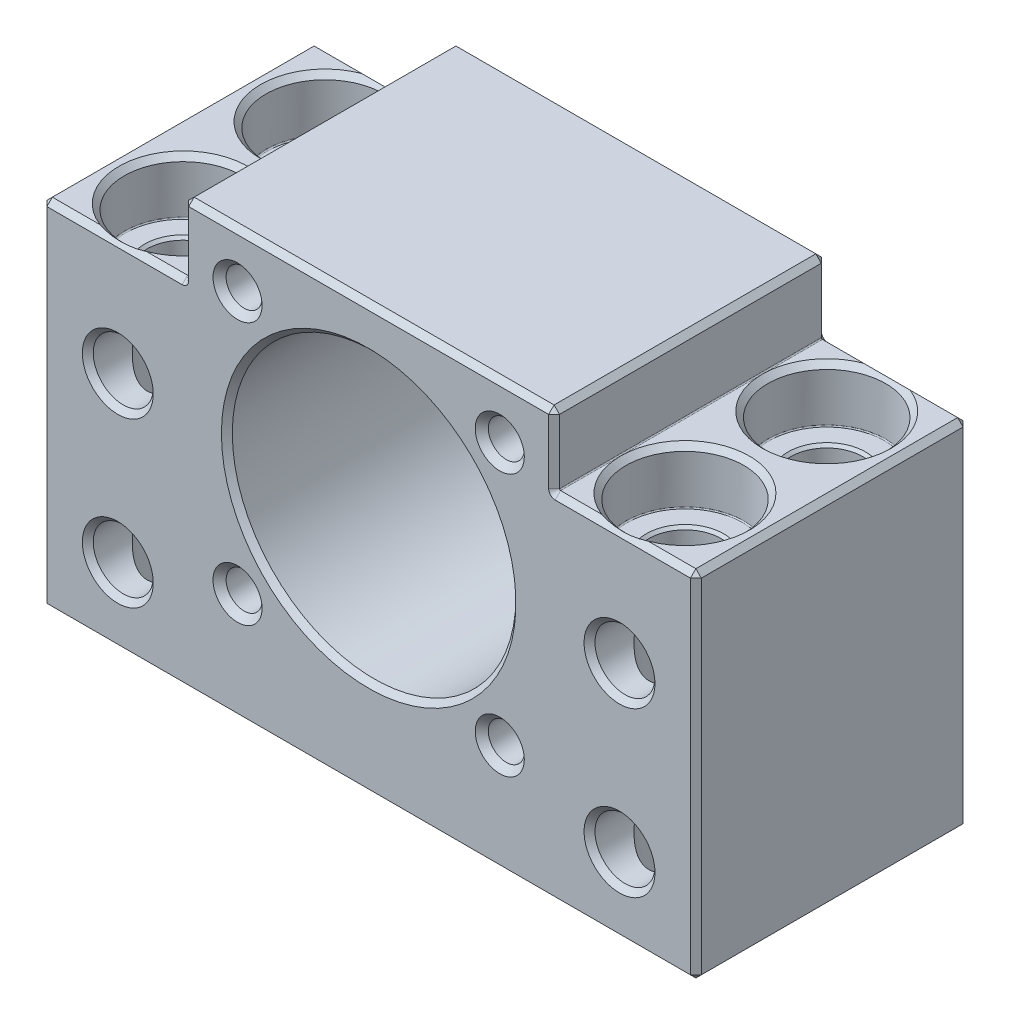
SolidWorks part; units mm, degrees
material "1023 Carbon Steel Sheet (SS)"
ref_plane "Front Plane" through (0, 0, 0) normal (0, 0, 1) x (1, 0, 0)
ref_plane "Top Plane" through (0, 0, 0) normal (0, 1, 0) x (1, 0, 0)
ref_plane "Right Plane" through (0, 0, 0) normal (1, 0, 0) x (0, 0, -1)
sketch "BK Body Sketch" plane through (0, 0, 0) normal (0, 0, 1) x (1, 0, 0)
  line L0 (30, -22) -> (-30, -22)
  line L1 (-30, -22) -> (-30, 10.5)
  line L2 (-30, 10.5) -> (-17, 10.5)
  line L3 (-17, 10.5) -> (-17, 17)
  line L4 (-17, 17) -> (17, 17)
  line L5 (17, 17) -> (17, 10.5)
  line L6 (17, 10.5) -> (30, 10.5)
  line L7 (30, 10.5) -> (30, -22)
  point P2 (0, -22)
  point P9 (0, 17)
  dimension "B" = 60
  dimension "B1" = 34
  dimension "H2" = 22
  dimension "H1" = 32.5
  dimension "H" = 39
extrude "BK Body" add sketch "BK Body Sketch" along normal mid plane 25
sketch "BK B-Flange" plane through (0, 0, 0) normal (0, 0, 1) x (1, 0, 0)
  circle A0 centre (0, 0) radius 11
  dimension "DOS" = 22
extrude "BK Flange" cut sketch "BK B-Flange" against normal through all both and the other way through all
sketch "BK B-Hole" plane through (0, 0, 12.5) normal (0, 0, 1) x (1, 0, 0)
  circle A0 centre (0, 0) radius 11 construction
  circle A1 centre (0, 0) radius 11
  circle A2 centre (0, 0) radius 13
  dimension "DO" = 26
extrude "BK Bearing" cut sketch "BK B-Hole" against normal offset from surface (20 mm away) 5 up to face at (11, 0, -12.5)
hole_wizard "Vertical Holes" positions "Sketch1" profile "Sketch2" counterbore size "M6" standard "ISO" end condition through all
sketch "Sketch1" plane through (0, 10.5, 0) normal (0, 1, 0) x (1, 0, 0)
  line L0 (23, 6.5) -> (-23, 6.5) construction
  line L3 (-17, 12.5) -> (-30, 12.5) construction
  point P0 (-23, 6.5)
  point P2 (-23, -6.5)
  point P4 (23, 6.5)
  point P6 (23, -6.5)
  point P11 (0, 6.5)
  dimension "P" = 46
  dimension "C1" = 13
  dimension "C2" = 6
sketch "Sketch2" plane through (-23, 10.5, -6.5) normal (1, 0, 0) x (0, 0, 1)
  line L0 (0, 0) -> (0, 32.5)
  line L1 (3.3, 32) -> (3.8, 32.5)
  line L2 (3.3, 32) -> (3.3, 5.25)
  line L3 (3.3, 5.25) -> (3.55, 5)
  line L4 (3.55, 5) -> (5.4, 5)
  line L5 (5.4, 5) -> (5.4, 0.5)
  line L6 (5.4, 0.5) -> (5.9, 0)
  line L7 (5.9, 0) -> (0, 0)
  line L8 (-5.4, 0.5) -> (-5.9, 0) construction
  line L9 (-3.3, 5.25) -> (-3.55, 5) construction
  line L11 (0, -6.35) -> (0, 107.95) construction
  line L12 (3.8, 32.5) -> (0, 32.5)
  line L13 (-3.3, 32) -> (-3.8, 32.5) construction
  dimension "Thru Hole Dia." = 6.6
  dimension "Thru Hole Depth" = 32.5
  dimension "C'Bore Dia." = 10.8
  dimension "C'Bore Depth" = 5
  dimension "Near C'Sink Dia." = 11.8
  dimension "Near C'Sink Angle" = 90
  dimension "Mid C'Sink Dia." = 7.1
  dimension "Mid C'Sink Angle" = 90
  dimension "Far C'Sink Dia." = 7.6
  dimension "Far C'Sink Angle" = 90
hole_wizard "Horizontal Holes" positions "Sketch3" profile "Sketch4" hole size "M5" standard "ISO" end condition through all
sketch "Sketch3" plane through (0, 0, 12.5) normal (0, 0, 1) x (1, 0, 0)
  line L0 (23, 0) -> (-23, 0) construction
  point P0 (-23, 0)
  point P2 (-23, -15)
  point P4 (23, 0)
  point P6 (23, -15)
  point P12 (0, 0)
  dimension "P" = 46
  dimension "E" = 15
sketch "Sketch4" plane through (-23, 0, 12.5) normal (1, 0, 0) x (0, -1, 0)
  line L0 (0, 0) -> (0, 25)
  line L1 (0, 25) -> (3.25, 25)
  line L2 (2.75, 24.5) -> (2.75, 0.5)
  line L3 (2.75, 0.5) -> (3.25, 0)
  line L5 (3.25, 0) -> (0, 0)
  line L6 (-2.75, 0.5) -> (-3.25, 0) construction
  line L7 (3.25, 25) -> (2.75, 24.5)
  line L8 (-3.25, 25) -> (-2.75, 24.5) construction
  line L11 (0, -6.35) -> (0, 107.95) construction
  dimension "Near C'Sink Angle" = 90
  dimension "Far C'Sink Angle" = 90
  dimension "Thru Hole Dia." = 5.5
  dimension "Thru Hole Depth" = 25
  dimension "Near C'Sink Dia." = 6.5
  dimension "Far C'Sink Dia." = 6.5
hole_wizard "Flange Holes" positions "Sketch5" profile "Sketch6" tap size "M4" standard "ISO"
sketch "Sketch5" plane through (0, 0, 12.5) normal (0, 0, 1) x (1, 0, 0)
  line L0 (12.0208, 12.0208) -> (-12.0208, -12.0208) construction
  line L1 (-12.0208, -12.0208) -> (-12.0208, 12.0208) construction
  line L3 (12.0208, 12.0208) -> (-12.0208, 12.0208) construction
  point P0 (-12.0208, 12.0208)
  point P2 (12.0208, 12.0208)
  point P4 (12.0208, -12.0208)
  point P6 (-12.0208, -12.0208)
  point P13 (0, 0)
  dimension "rf" = 34
sketch "Sketch6" plane through (-12.0208, 12.0208, 12.5) normal (1, 0, 0) x (0, -1, 0)
  line L0 (0, 0) -> (0, 12.4914)
  line L1 (0, 12.4914) -> (1.65, 11.5)
  line L2 (1.65, 11.5) -> (1.65, 0.6)
  line L3 (1.65, 0.6) -> (2.25, 0)
  line L5 (2.25, 0) -> (0, 0)
  line L6 (-1.65, 0.6) -> (-2.25, 0) construction
  line L10 (0, 12.4914) -> (-1.65, 11.5) construction
  line L11 (0, -6.35) -> (0, 107.95) construction
  dimension "Tap Drill Dia." = 3.3
  dimension "Tap Drill Depth" = 11.5
  dimension "Near C'Sink Dia." = 4.5
  dimension "Near C'Sink Angle" = 90
  dimension "Drill Angle" = 118
cosmetic thread "Hole Thread1" parameters "D1"=8, "D2"=4
cosmetic thread "Hole Thread2" parameters "D1"=8, "D2"=4
cosmetic thread "Hole Thread3" parameters "D1"=8, "D2"=4
cosmetic thread "Hole Thread4" parameters "D1"=8, "D2"=4
fillet "Bearing Fillet" radius 0.15 1 edges at (-13, 0, -7.5)
fillet "Production Fillet" radius 0.1 6 edges at (-17, 10.5, 0) (17, 10.5, 0) (-23, 5.5, 11.9) (-23, 5.5, -1.1) (23, 5.5, 11.9) (23, 5.5, -1.1)
chamfer "Aesthetic Chamfer" distance 0.5 angle 45 29 edges at (17, 17, 0) (0, 17, 12.5) (-17, 17, 0) (0, 17, -12.5) (-17, 13.8, -12.5) (17, 13.8, -12.5) (17, 13.8, 12.5) (-17, 13.8, 12.5) (-17.0293, 10.5293, -12.5) (17.0293, 10.5293, -12.5) (17.0293, 10.5293, 12.5) (-17.0293, 10.5293, 12.5) (-30, 10.5, 0) (-30, -22, 0) (-23.55, 10.5, -12.5) (-30, -5.75, -12.5) (30, -22, 0) (0, -22, -12.5) (30, -5.75, -12.5) (23.55, 10.5, -12.5) (30, 10.5, 0) (23.55, 10.5, 12.5) (30, -5.75, 12.5) (0, -22, 12.5) (-30, -5.75, 12.5) (-23.55, 10.5, 12.5) (11, 0, -12.5) (-11, 0, -7.5) (13, 0, 12.5)
equation "\"Near C'Sink Dia.@Sketch2\"= \"C'Bore Dia.@Sketch2\" + 1"
equation "\"Mid C'Sink Dia.@Sketch2\"= \"Thru Hole Dia.@Sketch2\" + 0.5"
equation "\"Far C'Sink Dia.@Sketch2\"= \"Thru Hole Dia.@Sketch2\" + 1"
equation "\"rf@Sketch5\"= 2 * ( \"H@BK Body Sketch\" - \"H2@BK Body Sketch\" )'Flange Holes distance"
equation "\"Near C'Sink Dia.@Sketch4\"= \"Thru Hole Dia.@Sketch4\" + 1"
equation "\"Far C'Sink Dia.@Sketch4\"= \"Thru Hole Dia.@Sketch4\" + 1"
